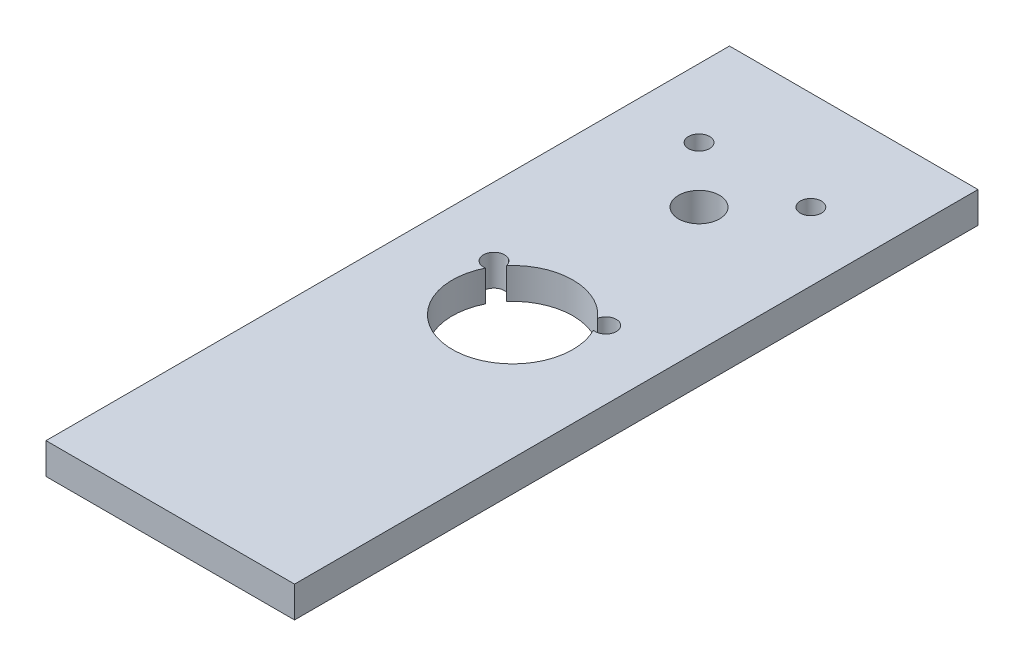
SolidWorks part; units mm, degrees
ref_plane "Front Plane" through (0, 0, 0) normal (0, 0, 1) x (1, 0, 0)
ref_plane "Top Plane" through (0, 0, 0) normal (0, 1, 0) x (1, 0, 0)
ref_plane "Right Plane" through (0, 0, 0) normal (1, 0, 0) x (0, 0, -1)
sketch "Sketch2" plane through (0, 0, 0) normal (0, 1, 0) x (1, 0, 0)
  line L1 (0, 0) -> (40, 0)
  line L2 (0, 0) -> (0, 110)
  line L3 (0, 110) -> (40, 110)
  line L4 (40, 0) -> (40, 110)
  dimension "D1" = 110
  dimension "D2" = 40
extrude "Boss-Extrude1" add sketch "Sketch2" along normal blind 5
sketch "Sketch3" plane through (0, 5, 0) normal (0, 1, 0) x (1, 0, 0)
  line L0 (20, 110) -> (20, 0) construction
  line L1 (40, 110) -> (0, 110) construction
  line L2 (0, 0) -> (40, 0) construction
  line L3 (0, 55) -> (40, 55) construction
  line L4 (0, 110) -> (0, 0) construction
  line L5 (40, 0) -> (40, 110) construction
  circle A0 centre (20, 85.1) radius 3.3
  circle A1 centre (20, 55.1) radius 9.7
  dimension "D1" = 6.6
  dimension "D4" = 19.4
  dimension "D2" = 24.9
  dimension "D3" = 30
extrude "Cut-Extrude1" cut sketch "Sketch3" against normal through all contours A0 | A1
sketch "Sketch5" plane through (0, 5, 0) normal (0, 1, 0) x (1, 0, 0)
  circle A0 centre (11, 94.1) radius 1.7
  circle A1 centre (20, 85.1) radius 3.3 construction
  circle A2 centre (11, 61.1) radius 1.7
  dimension "D1" = 3.4
  dimension "D2" = 9
  dimension "D3" = 9
  dimension "D4" = 24
extrude "Cut-Extrude2" cut sketch "Sketch5" against normal through all
ref_plane "Plane1" through (20, 0, 0) normal (1, 0, 0) x (0, 0, -1)
mirror "Mirror1" about plane through (20, 0, 0) normal (1, 0, 0) of "Cut-Extrude2"
